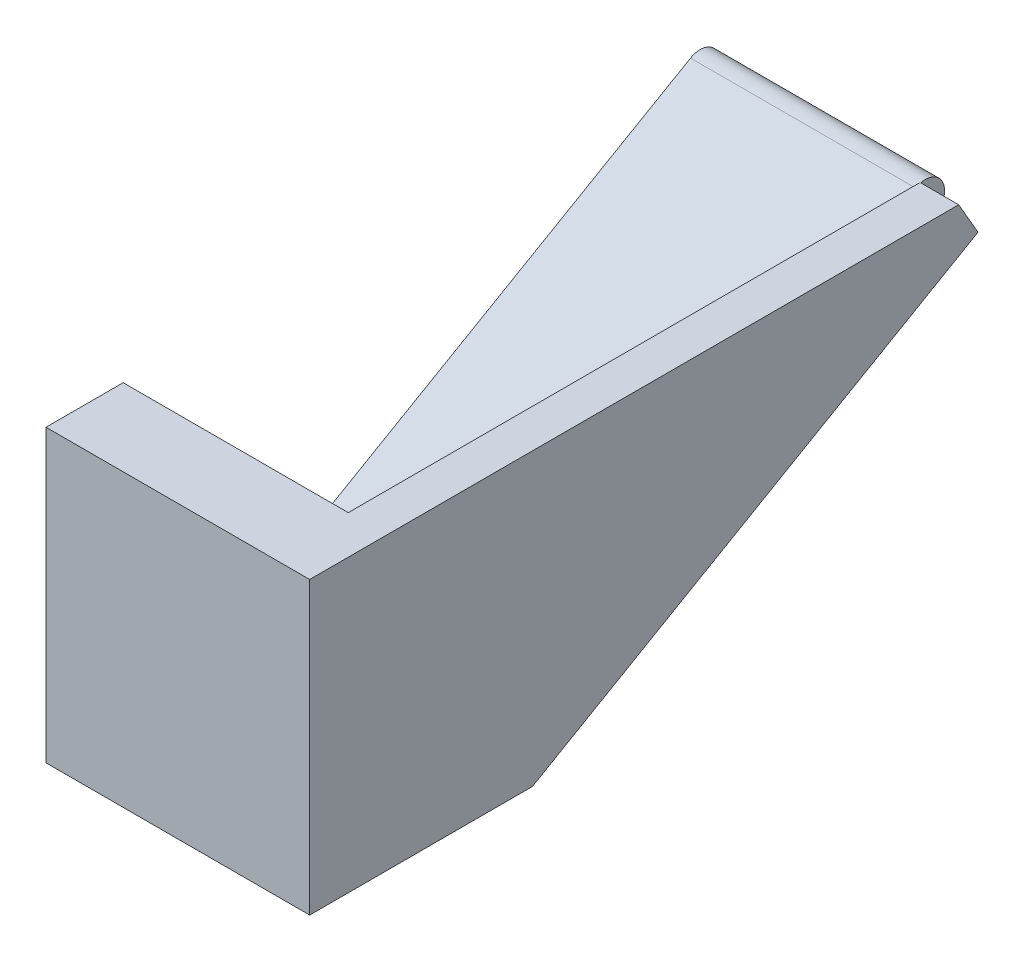
SolidWorks part; units mm, degrees
ref_plane "Front Plane" through (0, 0, 0) normal (0, 0, 1) x (1, 0, 0)
ref_plane "Top Plane" through (0, 0, 0) normal (0, 1, 0) x (1, 0, 0)
ref_plane "Right Plane" through (0, 0, 0) normal (1, 0, 0) x (0, 0, -1)
sketch "Sketch2" plane through (0, 0, 0) normal (1, 0, 0) x (0, 0, -1)
  line L0 (0, 0) -> (0, -22.5981)
  line L2 (6, -22.5981) -> (6, 0)
  line L3 (6, 0) -> (0, 0)
  line L4 (50.4615, 0) -> (51.9615, -2.5981) construction
  line L5 (51.9615, -2.5981) -> (17.3205, -22.5981) construction
  line L6 (17.3205, -22.5981) -> (15.8205, -20) construction
  line L7 (15.8205, -20) -> (50.4615, 0) construction
  line L8 (51.9615, -2.5981) -> (0, -32.5981) construction
  line L9 (0, -22.5981) -> (6, -22.5981)
  line L10 (15.7063, -21.798) -> (50.8634, -1.5) construction
  line L11 (14.9563, -20.4989) -> (50.1134, -0.201)
  line L12 (16.4563, -23.097) -> (51.6134, -2.799)
  line L13 (6, 0) -> (50.8634, 0) construction
  line L14 (15.7063, -23.298) -> (6, -23.298) construction
  arc A0 (14.9563, -20.4989) -> (16.4563, -23.097) centre (15.7063, -21.798) ccw
  arc A1 (51.6134, -2.799) -> (50.1134, -0.201) centre (50.8634, -1.5) ccw
  point P12 (33.2849, -11.649)
  point P20 (15.6193, -23.1472)
  dimension "D1" = 6
  dimension "D2" = 3
  dimension "D3" = 60
  dimension "D4" = 60
  dimension "D5" = 40
extrude "Boss-Extrude1" add sketch "Sketch2" along normal blind 17.5
sketch "Sketch3" plane through (17.5, 0, 0) normal (1, 0, 0) x (0, 0, -1)
  line L0 (0, 0) -> (6, 0)
  line L1 (6, 0) -> (50.4615, 0)
  line L2 (50.4615, 0) -> (51.9615, -2.5981)
  line L3 (51.9615, -2.5981) -> (17.3205, -22.5981)
  line L4 (17.3205, -22.5981) -> (0, -22.5981)
  line L5 (0, -22.5981) -> (0, 0)
extrude "Boss-Extrude2" add sketch "Sketch3" along normal blind 3
